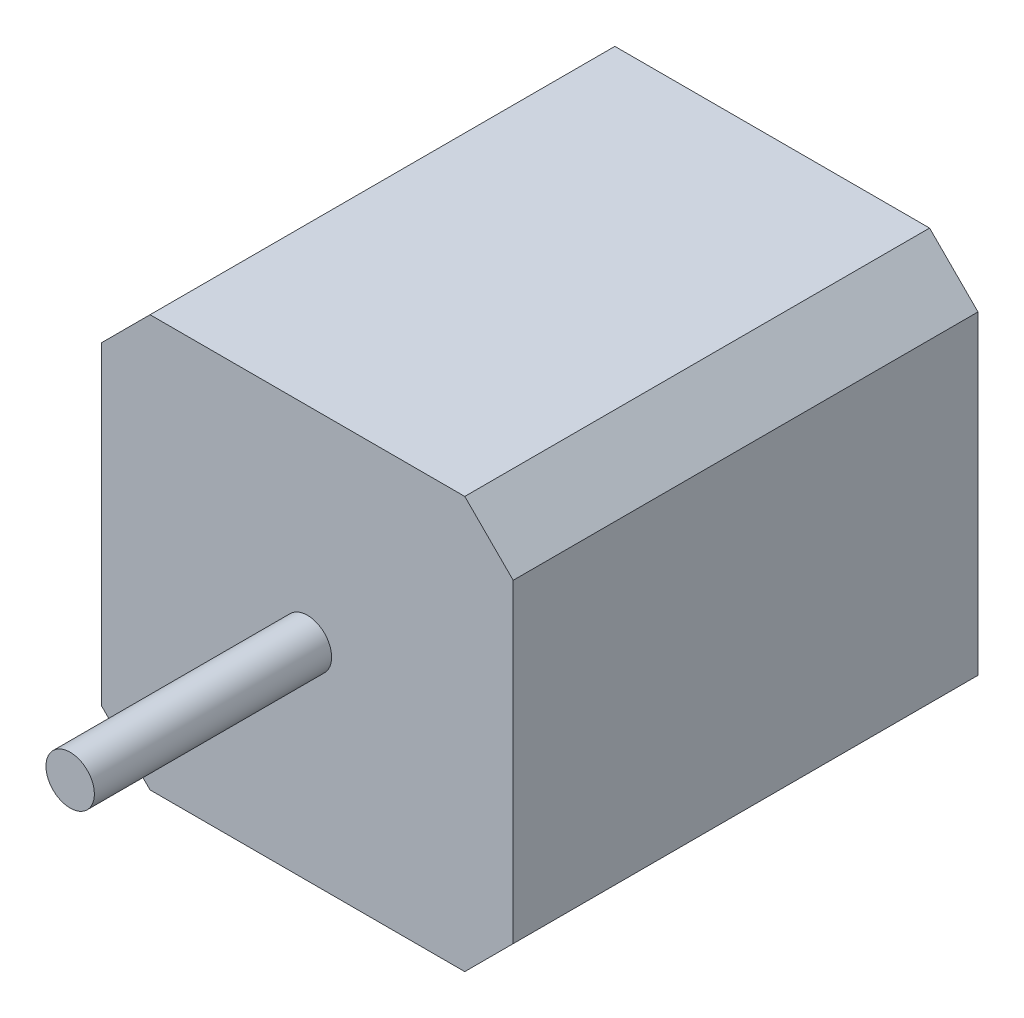
SolidWorks part; units mm, degrees
ref_plane "Front Plane" through (0, 0, 0) normal (0, 0, 1) x (1, 0, 0)
ref_plane "Top Plane" through (0, 0, 0) normal (0, 1, 0) x (1, 0, 0)
ref_plane "Right Plane" through (0, 0, 0) normal (1, 0, 0) x (0, 0, -1)
sketch "Sketch1" plane through (0, 0, 0) normal (0, 0, 1) x (1, 0, 0)
  line L1 (-41.6448, 27.598) -> (0.8552, 27.598)
  line L2 (-41.6448, 27.598) -> (-41.6448, -14.902)
  line L3 (-41.6448, -14.902) -> (0.8552, -14.902)
  line L4 (0.8552, 27.598) -> (0.8552, -14.902)
  dimension "D1" = 42.5
extrude "Boss-Extrude1" add sketch "Sketch1" along normal blind 48
chamfer "Chamfer1" distance 5 angle 45 4 edges at (0.8552, 27.598, 24) (0.8552, -14.902, 24) (-41.6448, -14.902, 24) (-41.6448, 27.598, 24)
sketch "Sketch2" plane through (0, 0, 48) normal (0, 0, 1) x (1, 0, 0)
  line L0 (-39.1448, 25.098) -> (-1.6448, -12.402) construction
  line L1 (-36.6448, 27.598) -> (-41.6448, 22.598) construction
  line L2 (-4.1448, -14.902) -> (0.8552, -9.902) construction
  circle A0 centre (-20.3948, 6.348) radius 2.5
extrude "Boss-Extrude2" add sketch "Sketch2" along normal blind 24.5
